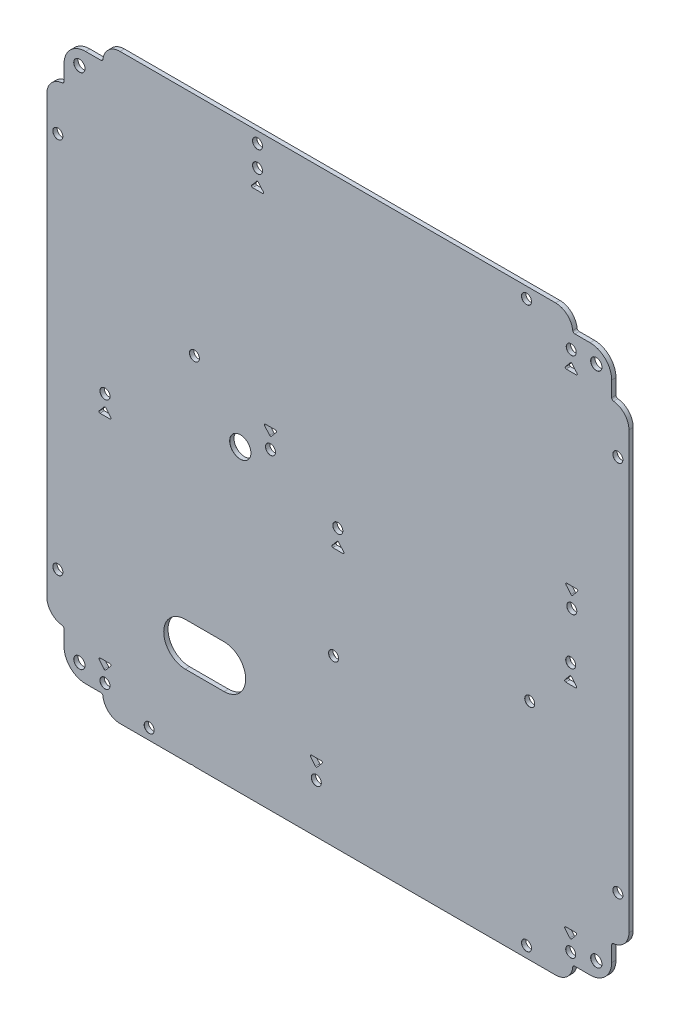
SolidWorks part; units mm, degrees
ref_plane "Front Plane" through (0, 0, 0) normal (0, 0, 1) x (1, 0, 0)
ref_plane "Top Plane" through (0, 0, 0) normal (0, 1, 0) x (1, 0, 0)
ref_plane "Right Plane" through (0, 0, 0) normal (1, 0, 0) x (0, 0, -1)
sketch "Sketch1" plane through (0, 0, 0) normal (0, 0, 1) x (1, 0, 0)
  line L1 (-135, -135) -> (135, -135)
  line L2 (-135, -135) -> (-135, 135)
  line L3 (-135, 135) -> (135, 135)
  line L4 (135, -135) -> (135, 135)
  line L5 (-135, -135) -> (135, 135) construction
  line L6 (-135, 135) -> (135, -135) construction
  point P0 (0, 0)
  dimension "D1" = 270
extrude "Boss-Extrude1" add sketch "Sketch1" along normal mid plane 2
sketch "Sketch5" plane through (0, 0, 0) normal (0, 0, 1) x (1, 0, 0)
  line L1 (-119.875, -119.875) -> (119.875, -119.875) construction
  line L2 (-119.875, -119.875) -> (-119.875, 119.875) construction
  line L3 (-119.875, 119.875) -> (119.875, 119.875) construction
  line L4 (119.875, -119.875) -> (119.875, 119.875) construction
  line L5 (-119.875, -119.875) -> (119.875, 119.875) construction
  line L6 (-119.875, 119.875) -> (119.875, -119.875) construction
  point P0 (0, 0)
  dimension "D1" = 239.75
hole_wizard "Ø5.2 (5.2) Diameter Hole1" positions "Sketch9" profile "Sketch11" hole size "Ø5.2" standard "ANSI Metric" end condition through all
sketch "Sketch9" plane through (0, 0, 1) normal (0, 0, 1) x (1, 0, 0)
  point P0 (119.875, 119.875)
  point P3 (119.875, -119.875)
  point P6 (-119.875, -119.875)
  point P9 (-119.875, 119.875)
sketch "Sketch11" plane through (119.875, 119.875, 1) normal (1, 0, 0) x (0, -1, 0)
  line L0 (0, 0) -> (0, 2)
  line L1 (0, 2) -> (2.625, 2)
  line L2 (2.6, 1.975) -> (2.6, 0.025)
  line L3 (2.6, 0.025) -> (2.625, 0)
  line L5 (2.625, 0) -> (0, 0)
  line L6 (-2.6, 0.025) -> (-2.625, 0) construction
  line L7 (2.625, 2) -> (2.6, 1.975)
  line L8 (-2.625, 2) -> (-2.6, 1.975) construction
  line L11 (0, -6.35) -> (0, 107.95) construction
  dimension "Thru Hole Dia." = 5.2
  dimension "Thru Hole Depth" = 2
  dimension "Near C'Sink Dia." = 5.25
  dimension "Near C'Sink Angle" = 90
  dimension "Far C'Sink Dia." = 5.25
  dimension "Far C'Sink Angle" = 90
sketch "Sketch12" plane through (0, 0, 0) normal (0, 0, 1) x (1, 0, 0)
  line L0 (-127, 109.9443) -> (-127, 117)
  line L1 (-117, 127) -> (-109.9443, 127)
  line L4 (-135, 101) -> (-135, 135)
  line L6 (-135, 135) -> (-101, 135)
  arc A0 (-127, 117) -> (-117, 127) centre (-117, 117) cw
  arc A1 (-108.9505, 127.8889) -> (-101, 135) centre (-101, 127) cw
  arc A2 (-127.8889, 108.9505) -> (-135, 101) centre (-127, 101) ccw
  arc A3 (-109.9443, 127) -> (-108.9505, 127.8889) centre (-109.9443, 128) ccw
  arc A4 (-127, 109.9443) -> (-127.8889, 108.9505) centre (-128, 109.9443) cw
  dimension "D1" = 10
  dimension "D2" = 8
  dimension "D5" = 1
  dimension "D3" = 34
  dimension "D4" = 8
extrude "Cut-Extrude1" cut sketch "Sketch12" against normal through all both and the other way through all
mirror "Mirror1" about plane through (0, 0, 0) normal (1, 0, 0) of "Cut-Extrude1" second plane through (0, 0, 0) second plane normal (0, 1, 0)
sketch "Sketch13" plane through (0, 0, 0) normal (0, 0, 1) x (1, 0, 0)
  line L1 (-129.875, -87.5) -> (129.875, -87.5) construction
  line L2 (-129.875, -87.5) -> (-129.875, 87.5) construction
  line L3 (-129.875, 87.5) -> (129.875, 87.5) construction
  line L4 (129.875, -87.5) -> (129.875, 87.5) construction
  line L5 (-129.875, -87.5) -> (129.875, 87.5) construction
  line L6 (-129.875, 87.5) -> (129.875, -87.5) construction
  point P0 (0, 0)
  dimension "D1" = 259.75
  dimension "D2" = 175
sketch "Sketch16" plane through (0, 0, 0) normal (0, 0, 1) x (1, 0, 0)
  line L0 (-135, 101) -> (-135, -101) construction
  line L1 (-87.5, -129.875) -> (87.5, -129.875) construction
  line L2 (-87.5, -129.875) -> (-87.5, 129.875) construction
  line L3 (-87.5, 129.875) -> (87.5, 129.875) construction
  line L4 (87.5, -129.875) -> (87.5, 129.875) construction
  line L5 (-87.5, -129.875) -> (87.5, 129.875) construction
  line L6 (-87.5, 129.875) -> (87.5, -129.875) construction
  point P0 (0, 0)
  point P6 (-37.25, 129.875)
  dimension "D1" = 175
  dimension "D2" = 259.75
  dimension "D3" = 97.75
hole_wizard "Ø4.6 (4.6) Diameter Hole1" positions "Sketch14" profile "Sketch15" hole size "Ø4.6" standard "ANSI Metric" end condition through all
sketch "Sketch14" plane through (0, 0, 1) normal (0, 0, 1) x (1, 0, 0)
  point P0 (129.875, 87.5)
  point P3 (129.875, -87.5)
  point P6 (-129.875, -87.5)
  point P9 (-129.875, 87.5)
  point P14 (-87.5, -129.875)
  point P17 (87.5, -129.875)
  point P20 (87.5, 129.875)
  point P24 (-37.25, 129.875)
sketch "Sketch15" plane through (129.875, 87.5, 1) normal (1, 0, 0) x (0, -1, 0)
  line L0 (0, 0) -> (0, 2)
  line L1 (0, 2) -> (2.325, 2)
  line L2 (2.3, 1.975) -> (2.3, 0.025)
  line L3 (2.3, 0.025) -> (2.325, 0)
  line L5 (2.325, 0) -> (0, 0)
  line L6 (-2.3, 0.025) -> (-2.325, 0) construction
  line L7 (2.325, 2) -> (2.3, 1.975)
  line L8 (-2.325, 2) -> (-2.3, 1.975) construction
  line L11 (0, -6.35) -> (0, 107.95) construction
  dimension "Thru Hole Dia." = 4.6
  dimension "Thru Hole Depth" = 2
  dimension "Near C'Sink Dia." = 4.65
  dimension "Near C'Sink Angle" = 90
  dimension "Far C'Sink Dia." = 4.65
  dimension "Far C'Sink Angle" = 90
sketch "Sketch17" plane through (0, 0, 0) normal (0, 0, 1) x (1, 0, 0)
  line L0 (-70.75, -88) -> (-52.75, -88) construction
  line L1 (-70.75, -78) -> (-52.75, -78)
  line L2 (-70.75, -98) -> (-52.75, -98)
  line L3 (-101, -135) -> (101, -135) construction
  line L4 (-135, 101) -> (-135, -101) construction
  arc A0 (-70.75, -78) -> (-70.75, -98) centre (-70.75, -88) ccw
  arc A1 (-52.75, -98) -> (-52.75, -78) centre (-52.75, -88) ccw
  point P2 (-61.75, -88)
  dimension "D2" = 38
  dimension "D1" = 20
  dimension "D3" = 37
  dimension "D4" = 54.25
extrude "Cut-Extrude2" cut sketch "Sketch17" along normal through all both and the other way through all
hole_wizard "Ø9.8 (9.8) Diameter Hole1" positions "Sketch18" profile "Sketch19" hole size "Ø9.8" standard "ANSI Metric" end condition through all
sketch "Sketch18" plane through (0, 0, 1) normal (0, 0, 1) x (1, 0, 0)
  line L0 (-135, 101) -> (-135, -101) construction
  line L1 (101, 135) -> (-101, 135) construction
  point P0 (-45.25, 4)
  dimension "D1" = 89.75
  dimension "D2" = 131
sketch "Sketch19" plane through (-45.25, 4, 1) normal (1, 0, 0) x (0, -1, 0)
  line L0 (0, 0) -> (0, 2)
  line L1 (0, 2) -> (4.925, 2)
  line L2 (4.9, 1.975) -> (4.9, 0.025)
  line L3 (4.9, 0.025) -> (4.925, 0)
  line L5 (4.925, 0) -> (0, 0)
  line L6 (-4.9, 0.025) -> (-4.925, 0) construction
  line L7 (4.925, 2) -> (4.9, 1.975)
  line L8 (-4.925, 2) -> (-4.9, 1.975) construction
  line L11 (0, -6.35) -> (0, 107.95) construction
  dimension "Thru Hole Dia." = 9.8
  dimension "Thru Hole Depth" = 2
  dimension "Near C'Sink Dia." = 9.85
  dimension "Near C'Sink Angle" = 90
  dimension "Far C'Sink Dia." = 9.85
  dimension "Far C'Sink Angle" = 90
hole_wizard "Ø4.6 (4.6) Diameter Hole2" positions "Sketch22" profile "Sketch23" hole size "Ø4.6" standard "ANSI Metric" end condition through all
sketch "Sketch22" plane through (0, 0, 1) normal (0, 0, 1) x (1, 0, 0)
  line L0 (-37.25, 129.875) -> (-37.25, 120) construction
  line L2 (101, 135) -> (-101, 135) construction
  line L3 (108.2499, 119.875) -> (119.875, 119.875) construction
  line L4 (-135, 101) -> (-135, -101) construction
  point P0 (-37.25, 120)
  point P9 (108.2499, 119.875)
  point P18 (-31.25, 10)
  point P23 (108.5, 16)
  point P24 (-67.4617, -137.1832)
  dimension "D1" = 15
  dimension "D2" = 243.2499
  dimension "D3" = 125
  dimension "D4" = 103.75
  dimension "D5" = 243.5
  dimension "D6" = 119
sketch "Sketch23" plane through (-37.25, 120, 1) normal (1, 0, 0) x (0, -1, 0)
  line L0 (0, 0) -> (0, 2)
  line L1 (0, 2) -> (2.325, 2)
  line L2 (2.3, 1.975) -> (2.3, 0.025)
  line L3 (2.3, 0.025) -> (2.325, 0)
  line L5 (2.325, 0) -> (0, 0)
  line L6 (-2.3, 0.025) -> (-2.325, 0) construction
  line L7 (2.325, 2) -> (2.3, 1.975)
  line L8 (-2.325, 2) -> (-2.3, 1.975) construction
  line L11 (0, -6.35) -> (0, 107.95) construction
  dimension "Thru Hole Dia." = 4.6
  dimension "Thru Hole Depth" = 2
  dimension "Near C'Sink Dia." = 4.65
  dimension "Near C'Sink Angle" = 90
  dimension "Far C'Sink Dia." = 4.65
  dimension "Far C'Sink Angle" = 90
hole_wizard "Ø4.6 (4.6) Diameter Hole3" positions "Sketch25" profile "Sketch26" hole size "Ø4.6" standard "ANSI Metric" end condition through all
sketch "Sketch25" plane through (0, 0, 1) normal (0, 0, 1) x (1, 0, 0)
  line L0 (-135, 101) -> (-135, -101) construction
  line L1 (-101, -135) -> (-68.2612, -135) construction
  line L3 (108, -6) -> (108, -122.25) construction
  line L5 (-108, -6) -> (-108, -122.25) construction
  point P0 (-108, -6)
  point P2 (0, -6)
  point P4 (108, -6)
  point P6 (-108, -122.25)
  point P8 (-10, -112.25)
  point P10 (108, -122.25)
  dimension "D1" = 27
  dimension "D2" = 135
  dimension "D3" = 243
  dimension "D4" = 129
  dimension "D5" = 12.75
  dimension "D8" = 125
  dimension "D9" = 22.75
sketch "Sketch26" plane through (-108, -6, 1) normal (1, 0, 0) x (0, -1, 0)
  line L0 (0, 0) -> (0, 2)
  line L1 (0, 2) -> (2.325, 2)
  line L2 (2.3, 1.975) -> (2.3, 0.025)
  line L3 (2.3, 0.025) -> (2.325, 0)
  line L5 (2.325, 0) -> (0, 0)
  line L6 (-2.3, 0.025) -> (-2.325, 0) construction
  line L7 (2.325, 2) -> (2.3, 1.975)
  line L8 (-2.325, 2) -> (-2.3, 1.975) construction
  line L11 (0, -6.35) -> (0, 107.95) construction
  dimension "Thru Hole Dia." = 4.6
  dimension "Thru Hole Depth" = 2
  dimension "Near C'Sink Dia." = 4.65
  dimension "Near C'Sink Angle" = 90
  dimension "Far C'Sink Dia." = 4.65
  dimension "Far C'Sink Angle" = 90
sketch "Sketch27" plane through (0, 0, 0) normal (0, 0, 1) x (1, 0, 0)
  line L0 (-39.5489, 111) -> (-34.9511, 111)
  line L1 (-34.5689, 111.8224) -> (-36.8679, 114.5471)
  line L2 (-37.6321, 114.5471) -> (-39.9311, 111.8224)
  line L3 (-37.25, 120) -> (-37.25, 111) construction
  arc A0 (-34.9511, 111) -> (-34.5689, 111.8224) centre (-34.9511, 111.5) ccw
  arc A1 (-39.5489, 111) -> (-39.9311, 111.8224) centre (-39.5489, 111.5) cw
  arc A2 (-36.8679, 114.5471) -> (-37.6321, 114.5471) centre (-37.25, 114.2247) ccw
  point P4 (-37.25, 111)
  point P7 (-33.875, 111)
  point P10 (-40.625, 111)
  point P13 (-37.25, 115)
  dimension "D3" = 0.5
  dimension "D1" = 6.75
  dimension "D2" = 4
  dimension "D4" = 9
extrude "Cut-Extrude3" cut sketch "Sketch27" along normal through all both and the other way through all
sketch "Sketch28" plane through (0, 0, 0) normal (0, 0, 1) x (1, 0, 0)
  point P0 (-37.25, 120)
  point P1 (108.2499, 119.875)
  point P3 (108, -6)
  point P5 (0, -6)
  point P7 (-108, -6)
pattern_sketch "Sketch-Pattern1" of "Cut-Extrude3" driven by "Sketch28"
sketch "Sketch29" plane through (0, 0, 0) normal (0, 0, 1) x (1, 0, 0)
  line L0 (-31.25, 10) -> (-31.25, 19) construction
  line L1 (-33.5489, 19) -> (-28.9511, 19)
  line L2 (-28.5689, 18.1776) -> (-30.8679, 15.4529)
  line L3 (-31.6321, 15.4529) -> (-33.9311, 18.1776)
  line L4 (-37.25, 120) -> (-37.25, 111) construction
  line L5 (-39.5489, 111) -> (-34.9511, 111) construction
  line L6 (-37.6321, 114.5471) -> (-39.9311, 111.8224) construction
  arc A0 (-28.9511, 19) -> (-28.5689, 18.1776) centre (-28.9511, 18.5) cw
  arc A1 (-30.8679, 15.4529) -> (-31.6321, 15.4529) centre (-31.25, 15.7753) cw
  arc A2 (-33.5489, 19) -> (-33.9311, 18.1776) centre (-33.5489, 18.5) ccw
  arc A3 (-34.9511, 111) -> (-34.5689, 111.8224) centre (-34.9511, 111.5) ccw construction
  point P6 (-31.25, 19)
  point P18 (-31.25, 15)
extrude "Cut-Extrude4" cut sketch "Sketch29" against normal through all both and the other way through all
sketch "Sketch30" plane through (0, 0, 0) normal (0, 0, 1) x (1, 0, 0)
  point P0 (-31.25, 10)
  point P1 (108.5, 16)
  point P3 (108, -122.25)
  point P5 (-10, -112.25)
  point P7 (-108, -122.25)
pattern_sketch "Sketch-Pattern2" of "Cut-Extrude4" driven by "Sketch30"
hole_wizard "Ø4.6 (4.6) Diameter Hole4" positions "Sketch31" profile "Sketch32" hole size "Ø4.6" standard "ANSI Metric" end condition through all
sketch "Sketch31" plane through (0, 0, 1) normal (0, 0, 1) x (1, 0, 0)
  line L0 (-135, 101) -> (-135, -101) construction
  line L1 (101, 135) -> (-101, 135) construction
  point P0 (-66.5, 30)
  point P2 (-2, -58.25)
  point P4 (89, -31)
  dimension "D1" = 68.5
  dimension "D2" = 105
  dimension "D3" = 133
  dimension "D4" = 224
  dimension "D5" = 193.25
  dimension "D6" = 166
sketch "Sketch32" plane through (-66.5, 30, 1) normal (1, 0, 0) x (0, -1, 0)
  line L0 (0, 0) -> (0, 2)
  line L1 (0, 2) -> (2.325, 2)
  line L2 (2.3, 1.975) -> (2.3, 0.025)
  line L3 (2.3, 0.025) -> (2.325, 0)
  line L5 (2.325, 0) -> (0, 0)
  line L6 (-2.3, 0.025) -> (-2.325, 0) construction
  line L7 (2.325, 2) -> (2.3, 1.975)
  line L8 (-2.325, 2) -> (-2.3, 1.975) construction
  line L11 (0, -6.35) -> (0, 107.95) construction
  dimension "Thru Hole Dia." = 4.6
  dimension "Thru Hole Depth" = 2
  dimension "Near C'Sink Dia." = 4.65
  dimension "Near C'Sink Angle" = 90
  dimension "Far C'Sink Dia." = 4.65
  dimension "Far C'Sink Angle" = 90
sketch "Sketch33" plane through (0, 0, 0) normal (0, 0, 1) x (1, 0, 0)
  line L0 (-66.6621, -135) -> (101, -135) construction
  line L1 (-111.75, -125) -> (111.75, -125)
  line L2 (-111.75, -125) -> (-111.75, -1.5)
  line L3 (-111.75, -1.5) -> (111.75, -1.5)
  line L4 (111.75, -125) -> (111.75, -1.5)
  line L5 (-101, -135) -> (-68.2612, -135) construction
  line L6 (-110.5, -12) -> (-98, -12)
  line L7 (-110.5, -12) -> (-110.5, -81.5)
  line L8 (-110.5, -81.5) -> (-98, -81.5)
  line L9 (-98, -12) -> (-98, -81.5)
  line L10 (-95.5, -12) -> (-83, -12)
  line L11 (-95.5, -12) -> (-95.5, -81.5)
  line L12 (-95.5, -81.5) -> (-83, -81.5)
  line L13 (-83, -12) -> (-83, -81.5)
  line L14 (-135, 101) -> (-135, -101) construction
  line L16 (-26.25, -14) -> (-25.25, -14)
  line L17 (-26.25, -14) -> (-26.25, -20.5)
  line L18 (-26.25, -20.5) -> (-25.25, -20.5)
  line L19 (-25.25, -14) -> (-25.25, -20.5)
  line L20 (-13.5, -14) -> (-12.5, -14)
  line L21 (-13.5, -14) -> (-13.5, -20.5)
  line L22 (-13.5, -20.5) -> (-12.5, -20.5)
  line L23 (-12.5, -14) -> (-12.5, -20.5)
  point P0 (0, -1.5)
  point P29 (-12.5, -17.25)
  dimension "D1" = 10
  dimension "D2" = 123.5
  dimension "D3" = 223.5
  dimension "D4" = 12.5
  dimension "D5" = 27.5
  dimension "D6" = 69.5
  dimension "D7" = 123
  dimension "D8" = 52
  dimension "D9" = 1
  dimension "D10" = 6.5
  dimension "D11" = 122.5
  dimension "D12" = 111
  dimension "D13" = 13.75
sketch "Sketch35" plane through (0, 0, 0) normal (0, 0, 1) x (1, 0, 0)
  circle A0 centre (-70.75, -88) radius 7.5
  circle A1 centre (-52.75, -88) radius 7.5
  dimension "D1" = 15
sketch "Sketch34" plane through (0, 0, 0) normal (0, 0, 1) x (1, 0, 0)
  line L0 (-32.125, -12.5) -> (-19.375, -12.5)
  line L1 (-19.375, -12.5) -> (-6.625, -12.5)
  line L2 (-26.25, -14) -> (-25.25, -14) construction
  line L3 (-13.5, -14) -> (-12.5, -14) construction
  line L4 (-44.1682, -104.5679) -> (-79.3318, -104.5679)
  line L7 (-70.75, -98) -> (-52.75, -98) construction
  text T0 "+12V"
  text T1 "GND"
  text T2 "+12v     GND"
  point P4 (-25.75, -12.5)
  point P7 (-25.75, -14)
  point P8 (-13, -12.5)
  point P11 (-13, -14)
  point P17 (-61.75, -104.5679)
  point P21 (-61.75, -98)
  dimension "D1" = 1.5
sketch "Sketch36" plane through (0, 0, 0) normal (0, 0, 1) x (1, 0, 0)
  line L1 (-104.25, -12) -> (-104.25, -81.5)
  line L2 (-110.5, -12) -> (-98, -12) construction
  line L3 (-110.5, -81.5) -> (-98, -81.5) construction
  line L4 (-89.25, -12) -> (-89.25, -81.5)
  line L5 (-95.5, -12) -> (-83, -12) construction
  line L6 (-95.5, -81.5) -> (-83, -81.5) construction
  text T0 "to Spraybox"
  text T1 "to fluid junction box"
sketch "Sketch37" plane through (0, 0, 0) normal (0, 0, 1) x (1, 0, 0)
  line L0 (-70.75, -98) -> (-52.75, -98) construction
  line L1 (-82.25, -117.5) -> (-41.25, -117.5)
  line L2 (-82.25, -117.5) -> (-82.25, -72.5)
  line L3 (-82.25, -72.5) -> (-41.25, -72.5)
  line L4 (-41.25, -117.5) -> (-41.25, -72.5)
  line L5 (-111.75, -125) -> (111.75, -125) construction
  point P6 (-61.75, -98)
  point P7 (-61.75, -72.5)
  dimension "D1" = 41
  dimension "D2" = 45
  dimension "D3" = 52.5
